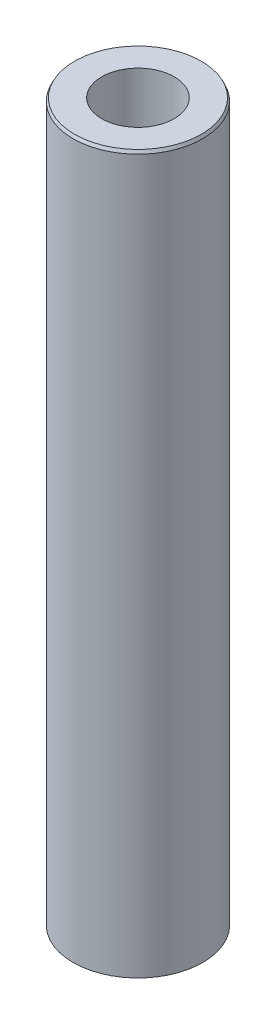
SolidWorks part; units mm, degrees
ref_plane "Front Plane" through (0, 0, 0) normal (0, 0, 1) x (1, 0, 0)
ref_plane "Top Plane" through (0, 0, 0) normal (0, 1, 0) x (1, 0, 0)
ref_plane "Right Plane" through (0, 0, 0) normal (1, 0, 0) x (0, 0, -1)
sketch "Sketch1" plane through (0, 0, 0) normal (0, 1, 0) x (1, 0, 0)
  circle A0 centre (0, 0) radius 37.5
  dimension "SHAFT_OD" = 75
extrude "Boss-Extrude1" add sketch "Sketch1" along normal blind 415.2265
sketch "Sketch2" plane through (0, 0, 0) normal (0, 1, 0) x (1, 0, 0)
  circle A0 centre (0, 0) radius 20.9946
  dimension "BORE_D" = 41.9892
extrude "Cut-Extrude1" cut sketch "Sketch2" along normal through all
chamfer "Chamfer1" distance 1.7844 angle 25.691 2 edges at (0, 415.2265, 37.5) (0, 0, 37.5) first distance on face at (0, 415.2265, 37.5) first distance on face at (0, 0, 20.9946)
